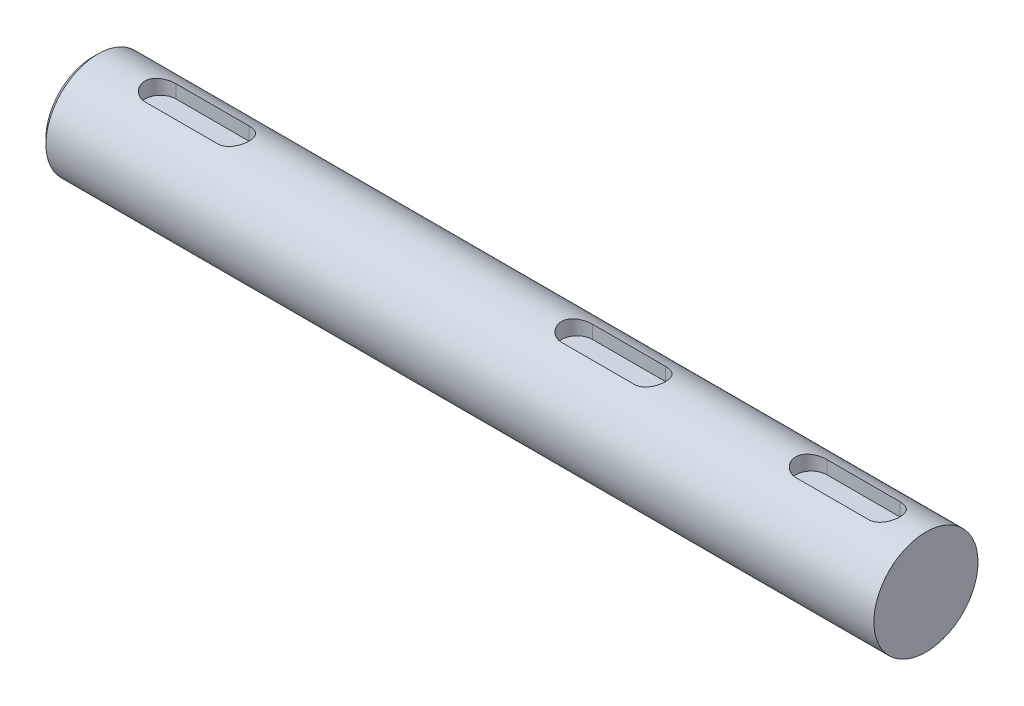
SolidWorks part; units mm, degrees
material "45"
ref_plane "前视基准面" through (0, 0, 0) normal (0, 0, 1) x (1, 0, 0)
ref_plane "上视基准面" through (0, 0, 0) normal (0, 1, 0) x (1, 0, 0)
ref_plane "右视基准面" through (0, 0, 0) normal (1, 0, 0) x (0, 0, -1)
ref_axis "基准轴1" through (88.99, 0, 0) along (-1, 0, 0)
sketch "草图1" plane through (0, 0, 0) normal (1, 0, 0) x (0, 0, -1)
  circle A0 centre (0, 0) radius 10
extrude "凸台-拉伸1" add sketch "草图1" along normal blind 200
ref_plane "基准面1" through (0, 10, 0) normal (0, 1, 0) x (1, 0, 0)
sketch "草图2" plane through (0, 10, 0) normal (0, 1, 0) x (1, 0, 0)
  line L0 (13, 3) -> (27, 3)
  line L1 (13, -3) -> (27, -3)
  arc A0 (13, 3) -> (13, -3) centre (13, 0) ccw
  arc A1 (27, 3) -> (27, -3) centre (27, 0) cw
  dimension "D1" = 3
  dimension "D2" = 14
extrude "切除-拉伸1" cut sketch "草图2" against normal blind 3
chamfer "倒角1" distance 1 angle 45 1 edges at (0, 0, -10)
chamfer "倒角2" distance 1 angle 45 1 edges at (200, 0, -10)
pattern_linear "阵列(线性)1" count 3 spacing 80 along (1, 0, 0) of "切除-拉伸1"
sketch "草图4" plane through (200, 0, 0) normal (1, 0, 0) x (0, 0, -1)
  circle A0 centre (0, 0) radius 10
extrude "切除-拉伸2" cut sketch "草图4" against normal blind 40
pattern_linear "阵列(线性)3" count 2 spacing 125 along (1, 0, 0) of "切除-拉伸1"
